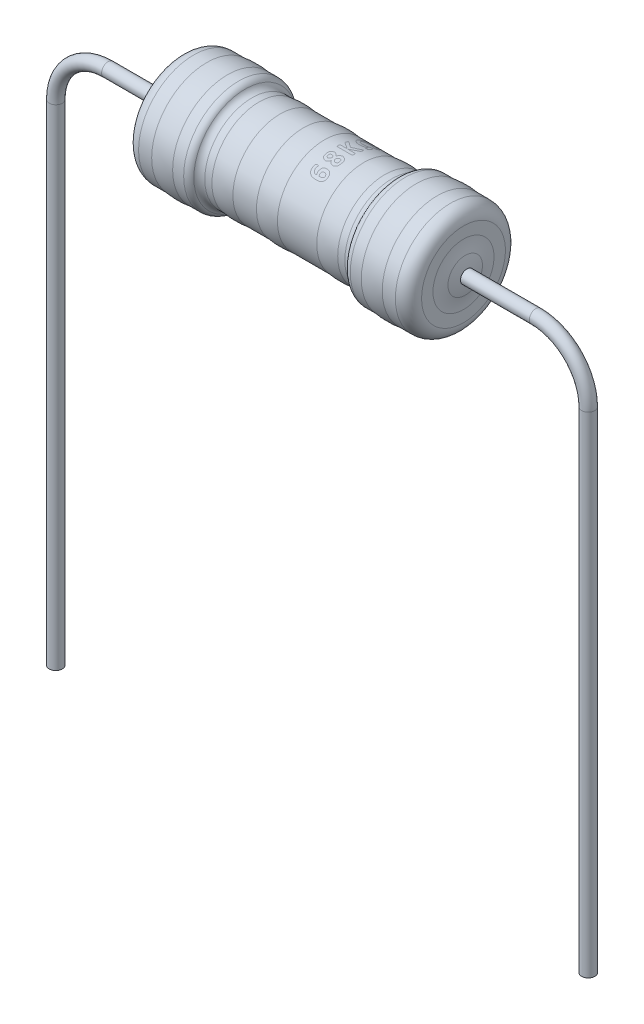
SolidWorks part; units mm, degrees
ref_plane "Front Plane" through (0, 0, 0) normal (0, 0, 1) x (1, 0, 0)
ref_plane "Top Plane" through (0, 0, 0) normal (0, 1, 0) x (1, 0, 0)
ref_plane "Right Plane" through (0, 0, 0) normal (1, 0, 0) x (0, 0, -1)
sketch "Sketch Set Wire Width" plane through (0, 0, 0) normal (0, 0, 1) x (1, 0, 0)
  line L0 (-8.16, 0) -> (8.16, 0)
  line L1 (-10.16, -2) -> (-10.16, -20.6984)
  line L2 (10.16, -2) -> (10.16, -20.6984)
  line L3 (-10.16, -20.6984) -> (10.16, -20.6984) construction
  line L4 (0, 0) -> (0, -20.6984) construction
  arc A0 (-8.16, 0) -> (-10.16, -2) centre (-8.16, -2) ccw
  arc A1 (8.16, 0) -> (10.16, -2) centre (8.16, -2) cw
  dimension "D2" = 2
  dimension "D3" = 60
  dimension "D1" = 20.32
sketch "Sketch Wire Diameter" plane through (0, 0, 0) normal (1, 0, 0) x (0, 0, -1)
  circle A0 centre (0, 0) radius 0.25
  dimension "D1" = 0.5
sweep "SET WIRE LENGTH" add profiles "Sketch Wire Diameter" path "Sketch Set Wire Width"
sketch "Sketch3" plane through (0, 0, 0) normal (0, 0, 1) x (1, 0, 0)
  line L0 (-5.4, 0) -> (5.4, 0)
  line L1 (0, 0) -> (0, 1.8) construction
  line L2 (-2.9, 1.8) -> (2.9, 1.8)
  line L3 (-5.4, 0) -> (-5.4, 1.6)
  line L4 (-4.9, 2.1) -> (-3.18, 2.1)
  line L5 (-2.9, 1.82) -> (-2.9, 1.8)
  line L6 (5.4, 0) -> (5.4, 1.6)
  line L7 (4.9, 2.1) -> (3.18, 2.1)
  line L8 (2.9, 1.82) -> (2.9, 1.8)
  arc A0 (-5.4, 1.6) -> (-4.9, 2.1) centre (-4.9, 1.6) cw
  arc A1 (5.4, 1.6) -> (4.9, 2.1) centre (4.9, 1.6) ccw
  arc A2 (-3.18, 2.1) -> (-2.9, 1.82) centre (-3.18, 1.82) cw
  arc A3 (3.18, 2.1) -> (2.9, 1.82) centre (3.18, 1.82) ccw
  dimension "D5" = 0.5
  dimension "D6" = 0.28
  dimension "D1" = 10.8
  dimension "D2" = 5.8
  dimension "D3" = 1.8
  dimension "D4" = 2.1
revolve "Revolve2" add sketch "Sketch3" angle 360 about L0
fillet "Fillet1" radius 0.3 2 edges at (2.9, 0, 1.8) (-2.9, 0, 1.8)
sketch "Sketch5" plane through (0, 0, 0) normal (0, 0, 1) x (1, 0, 0)
  line L0 (0, 0) -> (2, 0) construction
  line L1 (0, 0) -> (-0.3, 0) construction
  line L2 (-0.3, 0) -> (-2, 0) construction
  line L3 (-2, 0) -> (-4, 0) construction
  line L4 (2, 0) -> (4, 0) construction
  line L5 (-4, 0) -> (-4, 2.1) construction
  line L6 (-0.3, 0) -> (-0.3, 1.8) construction
  line L7 (-2, 0) -> (-2, 1.8) construction
  line L8 (2, 0) -> (2, 1.8) construction
  line L9 (4, 0) -> (4, 2.1) construction
  line L10 (-4, 2.1) -> (-4, 2.13) construction
  line L11 (-4.9, 2.1) -> (-3.18, 2.1) construction
  line L12 (4.9, 2.1) -> (3.18, 2.1) construction
  line L13 (-2.9, 1.8) -> (2.9, 1.8) construction
  line L14 (-2, 1.8) -> (-2, 1.83) construction
  line L17 (-4.4, 2.1) -> (-3.6, 2.1)
  line L19 (-5.4, 0) -> (5.4, 0) construction
  line L22 (-2.4, 1.8) -> (-1.6, 1.8) construction
  line L26 (-0.7, 1.8) -> (0.1, 1.8) construction
  line L30 (1.6, 1.8) -> (2.4, 1.8) construction
  line L34 (3.6, 2.1) -> (4.4, 2.1) construction
  line L36 (-0.3, 1.8) -> (-0.3, 1.83) construction
  line L37 (2, 1.8) -> (2, 1.83) construction
  line L38 (4, 2.1) -> (4, 2.13) construction
  arc A0 (-4.4, 2.1) -> (-3.6, 2.1) centre (-4, -0.5517) cw
  arc A1 (-2.4, 1.8) -> (-1.6, 1.8) centre (-2, -0.8517) cw construction
  arc A2 (-0.7, 1.8) -> (0.1, 1.8) centre (-0.3, -0.8517) cw construction
  arc A3 (1.6, 1.8) -> (2.4, 1.8) centre (2, -0.8517) cw construction
  arc A4 (3.6, 2.1) -> (4.4, 2.1) centre (4, -0.5517) cw construction
  dimension "D3" = 0.8
  dimension "D1" = 4
  dimension "D2" = 4
  dimension "D4" = 0.03
  dimension "D5" = 2
  dimension "D6" = 2
  dimension "D7" = 1.7
revolve "Band 1" add sketch "Sketch5" angle 360 about L2
sketch "Sketch8" plane through (0, 0, 0) normal (0, 0, 1) x (1, 0, 0)
  line L0 (-2.4, 1.8) -> (-1.6, 1.8) construction
  line L1 (-2.4, 1.8) -> (-1.6, 1.8)
  arc A0 (-1.6, 1.8) -> (-2.4, 1.8) centre (-2, -0.8517) ccw construction
  arc A1 (-1.6, 1.8) -> (-2.4, 1.8) centre (-2, -0.8517) ccw
revolve "Band 2" add sketch "Sketch8" angle 360 about L2
sketch "Sketch9" plane through (0, 0, 0) normal (0, 0, 1) x (1, 0, 0)
  line L0 (-0.7, 1.8) -> (0.1, 1.8) construction
  line L1 (-0.7, 1.8) -> (0.1, 1.8)
  arc A0 (0.1, 1.8) -> (-0.7, 1.8) centre (-0.3, -0.8517) ccw construction
  arc A1 (0.1, 1.8) -> (-0.7, 1.8) centre (-0.3, -0.8517) ccw
revolve "Band 3" add sketch "Sketch9" angle 360 about L2
sketch "Sketch10" plane through (0, 0, 0) normal (0, 0, 1) x (1, 0, 0)
  line L0 (1.6, 1.8) -> (2.4, 1.8) construction
  line L1 (1.6, 1.8) -> (2.4, 1.8)
  arc A0 (2.4, 1.8) -> (1.6, 1.8) centre (2, -0.8517) ccw construction
  arc A1 (2.4, 1.8) -> (1.6, 1.8) centre (2, -0.8517) ccw
revolve "Band 4" add sketch "Sketch10" angle 360 about L0
sketch "Sketch11" plane through (0, 0, 0) normal (0, 0, 1) x (1, 0, 0)
  line L0 (3.6, 2.1) -> (4.4, 2.1) construction
  line L1 (3.6, 2.1) -> (4.4, 2.1)
  arc A0 (4.4, 2.1) -> (3.6, 2.1) centre (4, -0.5517) ccw construction
  arc A1 (4.4, 2.1) -> (3.6, 2.1) centre (4, -0.5517) ccw
revolve "Band 5" add sketch "Sketch11" angle 360 about L4
sketch "Sketch12" plane through (0, 0, 0) normal (0, 0, 1) x (1, 0, 0)
  line L0 (-5.35, 0) -> (5.35, 0) construction
  line L1 (-5.35, 1) -> (-5.35, 0)
  line L2 (5.35, 1) -> (5.35, 0)
  line L3 (-5.35, 0) -> (-5.55, 0)
  line L4 (5.35, 0) -> (5.55, 0)
  arc A0 (-5.35, 1) -> (-5.55, 0) centre (-2.95, 0) ccw
  arc A1 (5.35, 1) -> (5.55, 0) centre (2.95, 0) cw
  dimension "D3" = 0.2
  dimension "D4" = 2.6
  dimension "D1" = 10.7
  dimension "D2" = 1
revolve "Revolve10" add sketch "Sketch12" angle 360 about L0
fillet "Fillet2" radius 2 2 edges at (5.4, 0, 0.8703) (-5.4, 0, -0.8703)
ref_plane "Plane2" through (0, 3, 0) normal (0, 1, 0) x (1, 0, 0)
sketch "Sketch13" plane through (0, 3, 0) normal (0, 1, 0) x (1, 0, 0)
  line L0 (0, 0) -> (1.15, 0) construction
  line L1 (1.15, 1.75) -> (1.15, -1.75) construction
  text T0 "68KΩ" font "Calibri" height 0.6
  dimension "D1" = 3.5
  dimension "D2" = 1.15
wrap "Wrap1" sketch "Sketch13" wrap type scribe source sketch "Sketch13" face at (0.1, 1.8, 0)
